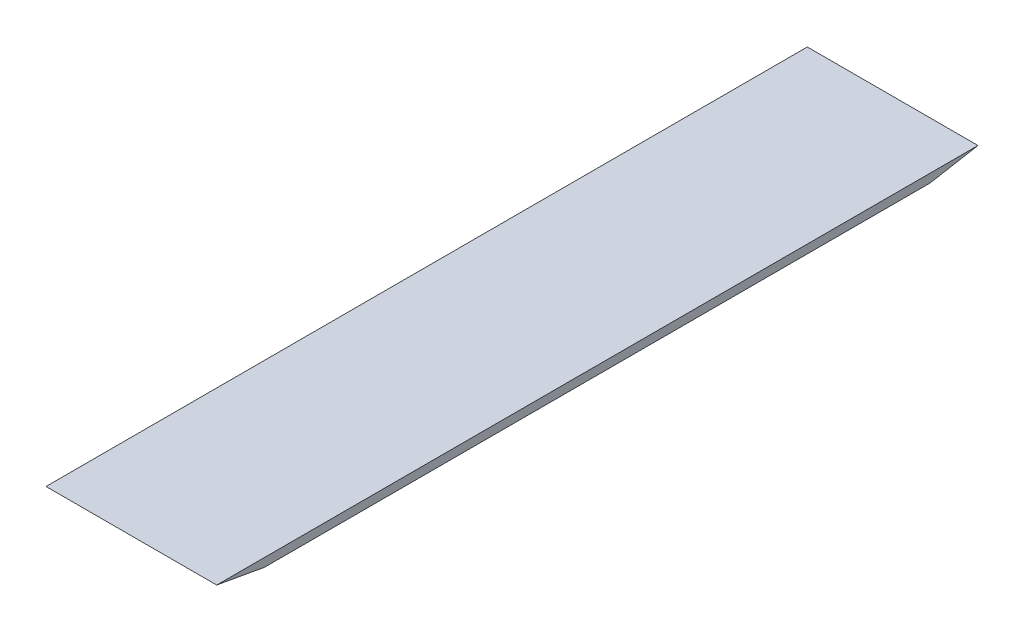
SolidWorks part; units mm, degrees
ref_plane "Front Plane" through (0, 0, 0) normal (0, 0, 1) x (1, 0, 0)
ref_plane "Top Plane" through (0, 0, 0) normal (0, 1, 0) x (1, 0, 0)
ref_plane "Right Plane" through (0, 0, 0) normal (1, 0, 0) x (0, 0, -1)
sketch "Sketch1" plane through (0, 0, 0) normal (1, 0, 0) x (0, 0, -1)
  line L0 (0, 0) -> (446, 0)
  line L1 (446, 0) -> (418, -5)
  line L2 (418, -5) -> (28, -5)
  line L3 (28, -5) -> (0, 0)
  dimension "D1" = 390
  dimension "D2" = 28
  dimension "D3" = 28
  dimension "D4" = 5
extrude "Boss-Extrude1" add sketch "Sketch1" along normal blind 100 contours L2 L3 L0 L1
